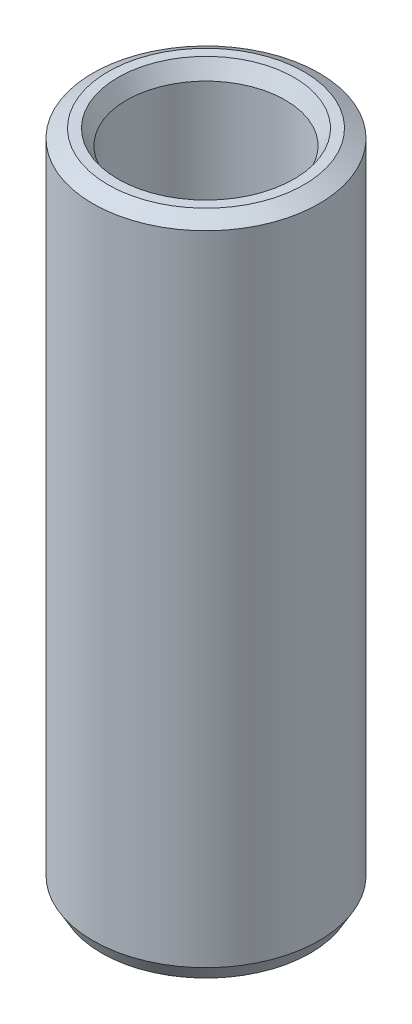
SolidWorks part; units mm, degrees
ref_plane "Front Plane" through (0, 0, 0) normal (0, 0, 1) x (1, 0, 0)
ref_plane "Top Plane" through (0, 0, 0) normal (0, 1, 0) x (1, 0, 0)
ref_plane "Right Plane" through (0, 0, 0) normal (1, 0, 0) x (0, 0, -1)
sketch "Sketch1" plane through (0, 0, 0) normal (0, 1, 0) x (1, 0, 0)
  circle A0 centre (0, 0) radius 50
  dimension "SLEEVE_OD" = 100
extrude "Boss-Extrude1" add sketch "Sketch1" along normal blind 292.566
sketch "Sketch2" plane through (0, 0, 0) normal (0, 1, 0) x (1, 0, 0)
  circle A0 centre (0, 0) radius 35.0257
  dimension "BORE_D" = 70.0514
extrude "Cut-Extrude1" cut sketch "Sketch2" along normal through all
chamfer "Chamfer1" distance 3.8804 angle 60 4 edges at (0, 292.566, 35.0257) (0, 0, 35.0257) (0, 0, 50) (0, 292.566, 50) first distance on face at (0, 292.566, 35.0257) first distance on face at (0, 0, 35.0257) first distance on face at (0, 292.566, 50)
